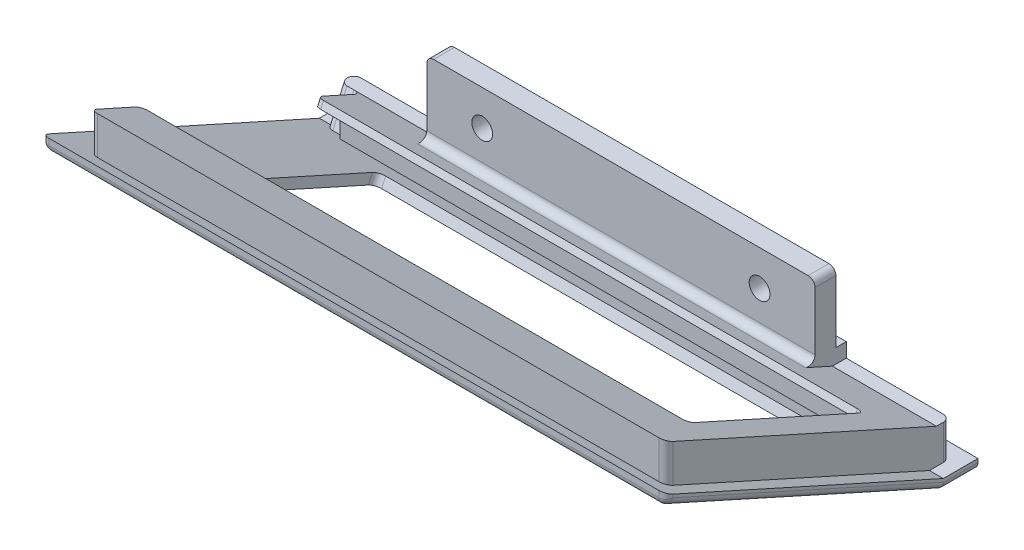
SolidWorks part; units mm, degrees
ref_plane "前视基准面" through (0, 0, 0) normal (0, 0, 1) x (1, 0, 0)
ref_plane "上视基准面" through (0, 0, 0) normal (0, 1, 0) x (1, 0, 0)
ref_plane "右视基准面" through (0, 0, 0) normal (1, 0, 0) x (0, 0, -1)
sketch "草图1" plane through (0, 0, 0) normal (0, 1, 0) x (1, 0, 0)
  line L1 (0, 0) -> (90, 0)
  line L2 (0, 0) -> (0, 45)
  line L3 (0, 45) -> (90, 45)
  line L4 (90, 0) -> (90, 45)
  dimension "D1" = 90
  dimension "D2" = 45
extrude "凸台-拉伸1" add sketch "草图1" along normal blind 60
sketch "草图2" plane through (90, 0, 0) normal (1, 0, 0) x (0, 0, -1)
  line L0 (0, 60) -> (0, 28)
  line L1 (0, 60) -> (0, 0) construction
  line L2 (0, 28) -> (40, 10)
  line L3 (40, 10) -> (45, 10)
  line L4 (45, 60) -> (45, 0) construction
  dimension "D1" = 32
  dimension "D2" = 5
  dimension "D3" = 50
extrude "切除-拉伸1" cut sketch "草图2" against normal through all and the other way through all
sketch "草图3" plane through (90, 0, 0) normal (1, 0, 0) x (0, 0, -1)
  line L0 (0, 26.4487) -> (39.8859, 8.5)
  line L1 (0, 28) -> (0, 0) construction
  line L2 (39.8859, 8.5) -> (45, 8.5)
  line L3 (45, 10) -> (45, 0) construction
  line L4 (45, 8.5) -> (45, 0)
  line L5 (45, 0) -> (0, 0)
  line L6 (0, 0) -> (0, 26.4487)
  line L8 (0, 28) -> (40, 10) construction
  line L9 (40, 10) -> (45, 10) construction
  dimension "D1" = 1.5
extrude "切除-拉伸2" cut sketch "草图3" against normal through all
ref_plane "基准面4" through (0, 34, 0) normal (0, 1, 0) x (1, 0, 0)
sketch "草图4" plane through (0, 34, 0) normal (0, 1, 0) x (1, 0, 0)
  line L0 (90, 45) -> (0, 45) construction
  line L1 (2, 2) -> (88, 2)
  line L2 (2, 2) -> (2, 43)
  line L3 (2, 43) -> (88, 43)
  line L4 (88, 2) -> (88, 43)
  line L5 (0, 40) -> (0, 0) construction
  line L6 (90, 0) -> (90, 40) construction
  line L7 (90, 0) -> (0, 0) construction
  line L9 (4, 4) -> (86, 4)
  line L10 (4, 4) -> (4, 38)
  line L11 (4, 38) -> (86, 38)
  line L12 (86, 4) -> (86, 38)
  dimension "D1" = 2
  dimension "D2" = 2
  dimension "D3" = 2
  dimension "D4" = 2
  dimension "D5" = 2
  dimension "D6" = 5
  dimension "D7" = 2
  dimension "D8" = 2
extrude "凸台-拉伸3" add sketch "草图4" against normal up to body
sketch "草图5" plane through (2, 0, 0) normal (-1, 0, 0) x (0, 0, 1)
  line L0 (-43, 15.0329) -> (-41, 15.0329)
  line L1 (-43, 10) -> (-43, 34) construction
  line L2 (-41, 15.0329) -> (-2, 32.5829)
  line L3 (-2, 27.1) -> (-2, 34) construction
  line L4 (-2, 32.5829) -> (-2, 34)
  line L5 (24.75, 34) -> (-24.75, 34) construction
  line L6 (-2, 34) -> (-43, 34)
  line L7 (-43, 34) -> (-43, 15.0329)
  line L8 (-45, 10) -> (-40, 10) construction
  line L9 (-2, 27.1) -> (-40, 10) construction
  line L10 (-40, 10) -> (0, 28) construction
  dimension "D1" = 5
  dimension "D2" = 2
extrude "切除-拉伸3" cut sketch "草图5" against normal through all
sketch "草图6" plane through (0, 21.9947, -9.8976) normal (0, -0.9119, 0.4104) x (1, 0, 0)
  line L0 (90, -32.8847) -> (90, 10.8536) construction
  line L1 (13, -27.5156) -> (85, -27.5156)
  line L2 (13, -27.5156) -> (13, 5.4844)
  line L3 (13, 5.4844) -> (85, 5.4844)
  line L4 (85, -27.5156) -> (85, 5.4844)
  point P6 (90, -11.0156)
  point P7 (85, -11.0156)
  dimension "D1" = 33
  dimension "D2" = 72
  dimension "D3" = 5
extrude "切除-拉伸4" cut sketch "草图6" against normal through all
sketch "草图9" plane through (4, 0, 0) normal (1, 0, 0) x (0, 0, -1)
  line L0 (4, 31.6829) -> (4, 30.5863)
  line L1 (38, 16.3829) -> (4, 31.6829) construction
  line L2 (4, 26.2) -> (4, 31.6829) construction
  line L3 (4, 30.5863) -> (38, 15.2863)
  line L4 (38, 10.9) -> (38, 16.3829) construction
  line L5 (38, 15.2863) -> (38, 16.3829)
  line L6 (38, 16.3829) -> (4, 31.6829)
  dimension "D1" = 1
extrude "凸台-拉伸8" add sketch "草图9" along normal up to surface (82 mm away) up to face at (86, 21.2915, -21)
sketch "草图10" plane through (0, 27.8444, -12.53) normal (0, 0.9119, -0.4104) x (1, 0, 0)
  line L0 (2, 31.2198) -> (2, -11.547) construction
  line L1 (5, -3.547) -> (84, -3.547)
  line L2 (5, -3.547) -> (5, 24.2198)
  line L3 (5, 24.2198) -> (84, 24.2198)
  line L4 (84, -3.547) -> (84, 24.2198)
  line L5 (88, 31.2198) -> (2, 31.2198) construction
  line L6 (88, -11.547) -> (2, -11.547) construction
  line L7 (88, -11.547) -> (88, 31.2198) construction
  dimension "D1" = 3
  dimension "D2" = 7
  dimension "D3" = 8
  dimension "D4" = 4
extrude "切除-拉伸5" cut sketch "草图10" against normal up to next
sketch "草图11" plane through (0, 27.8444, -12.53) normal (0, 0.9119, -0.4104) x (1, 0, 0)
  line L0 (2, 31.2198) -> (5, 31.2198)
  line L2 (2, -11.547) -> (5, -11.547)
  line L3 (5, -11.547) -> (5, 31.2198)
  line L4 (2, 31.2198) -> (2, -11.547)
  line L5 (88, 31.2198) -> (2, 31.2198) construction
  line L6 (88, -11.547) -> (2, -11.547) construction
  line L7 (2, 31.2198) -> (2, -11.547) construction
  line L8 (5, 24.2198) -> (5, -3.547) construction
extrude "切除-拉伸6" cut sketch "草图11" against normal up to surface (5 mm away) up to face at (45, 18.775, -20.5)
ref_plane "基准面5" through (45, 0, 0) normal (1, 0, 0) x (0, 0, -1)
sketch "草图12" plane through (45, 0, 0) normal (1, 0, 0) x (0, 0, -1)
  line L0 (43, 15.0329) -> (43, 17.0954)
  line L1 (41.5, 27.0954) -> (38.5, 27.0954)
  line L5 (41, 15.0329) -> (43, 15.0329)
  line L6 (38.5, 27.0954) -> (38.5, 15.0613)
  line L8 (38.5, 15.0613) -> (41, 15.0329)
  line L9 (43, 17.0954) -> (41.5, 17.0954)
  line L10 (41.5, 17.0954) -> (41.5, 27.0954)
  dimension "D1" = 1.5
  dimension "D2" = 3
  dimension "D3" = 10
extrude "凸台-拉伸9" add sketch "草图12" along normal mid plane 56
sketch "草图13" plane through (0, 0, -38.5) normal (0, 0, 1) x (1, 0, 0)
  line L1 (45, -12.9175) -> (45, 12.9175) construction
  line L2 (90, 10) -> (0, 10) construction
  circle A0 centre (25, 22) radius 1.5
  circle A1 centre (65, 22) radius 1.5
  dimension "D1" = 3
  dimension "D2" = 12
  dimension "D3" = 20
extrude "切除-拉伸7" cut sketch "草图13" against normal through all
fillet "圆角1" radius 1 12 edges at (85, 11.3484, -35.2799) (85, 24.8904, -5.1865) (13, 24.8904, -5.1865) (13, 11.3484, -35.2799) (90, 27.2243, 0) (0, 27.2243, 0) (0, 8.5, -42.443) (0, 17.4743, -19.943) (90, 8.5, -42.443) (90, 17.4743, -19.943) (45, 26.4487, 0) (45, 8.5, -39.8859)
fillet "圆角2" radius 1 3 edges at (17, 27.0954, -40) (73, 27.0954, -40) (45, 16.1579, -38.5)
fillet "圆角3" radius 1 10 edges at (88, 12.5165, -43) (2, 12.5165, -43) (84, 28.844, -9.0902) (84, 17.4495, -34.4114) (5, 12.7531, -39.9741) (5, 28.844, -9.0902) (5, 17.4495, -34.4114) (2, 12.7531, -39.9741) (5, 29.8415, -2) (88, 29.8415, -2)
sketch "草图14" plane through (0, 21.9947, -9.8976) normal (0, -0.9119, 0.4104) x (1, 0, 0)
  line L0 (8, 3.9844) -> (8, -26.0156) construction
  line L1 (9, 3.9844) -> (9, -26.0156)
  line L2 (7, 3.9844) -> (7, -26.0156)
  line L3 (13, 4.4844) -> (13, -26.5156) construction
  line L4 (4, -1.0156) -> (4, 3.9844) construction
  line L5 (3, -1.0156) -> (3, 3.9844)
  line L6 (5, -1.0156) -> (5, 3.9844)
  arc A0 (9, 3.9844) -> (7, 3.9844) centre (8, 3.9844) ccw
  arc A1 (7, -26.0156) -> (9, -26.0156) centre (8, -26.0156) ccw
  arc A2 (3, -1.0156) -> (5, -1.0156) centre (4, -1.0156) ccw
  arc A3 (5, 3.9844) -> (3, 3.9844) centre (4, 3.9844) ccw
  point P2 (8, -11.0156)
  point P9 (13, -11.0156)
  point P12 (4, 1.4844)
  dimension "D1" = 30
  dimension "D2" = 2
  dimension "D3" = 5
  dimension "D4" = 2
  dimension "D5" = 5
  dimension "D6" = 4
extrude "切除-拉伸8" cut sketch "草图14" against normal blind 1
